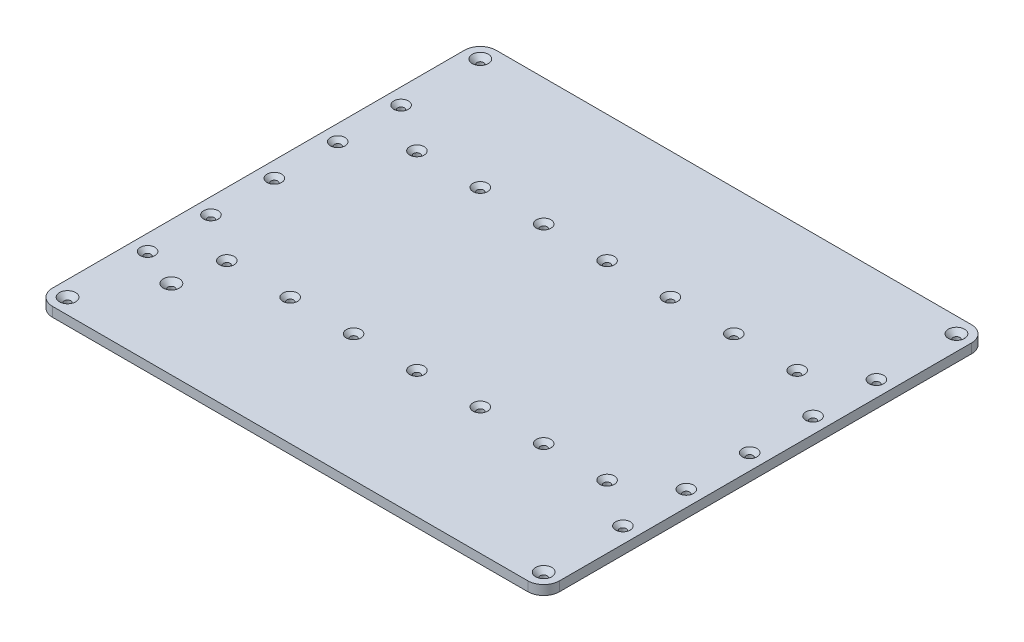
SolidWorks part; units mm, degrees
ref_plane "前视基准面" through (0, 0, 0) normal (0, 0, 1) x (1, 0, 0)
ref_plane "上视基准面" through (0, 0, 0) normal (0, 1, 0) x (1, 0, 0)
ref_plane "右视基准面" through (0, 0, 0) normal (1, 0, 0) x (0, 0, -1)
other "Configuration Table"
sketch "草图1" plane through (0, 0, 0) normal (0, 1, 0) x (1, 0, 0)
  line L1 (-150, -140) -> (150, -140)
  line L2 (-160, -130) -> (-160, 130)
  line L3 (-150, 140) -> (150, 140)
  line L4 (160, -130) -> (160, 130)
  line L5 (-160, -140) -> (-156.8729, -137.2638) construction
  line L6 (-160, 140) -> (-156.8729, 137.2638) construction
  line L8 (156.8729, 137.2638) -> (160, 140) construction
  line L9 (156.8729, -137.2638) -> (160, -140) construction
  arc A0 (150, -140) -> (160, -130) centre (150, -130) ccw
  arc A1 (-160, 130) -> (-150, 140) centre (-150, 130) cw
  arc A2 (-150, -140) -> (-160, -130) centre (-150, -130) cw
  arc A3 (150, 140) -> (160, 130) centre (150, 130) cw
  point P0 (0, 0)
  dimension "D3" = 10
  dimension "D1" = 320
  dimension "D2" = 280
extrude "凸台-拉伸1" add sketch "草图1" along normal mid plane 6
sketch "草图5" plane through (0, 3, 0) normal (0, 1, 0) x (1, 0, 0)
  line L0 (0, 0) -> (0, 142.7283) construction
  line L1 (160, 0) -> (-160, 0) construction
  line L2 (-160, 130) -> (-160, -130) construction
  line L3 (150, 140) -> (-150, 140) construction
  circle A0 centre (0, 60) radius 2.1
  circle A16 centre (40, 60) radius 2.1
  circle A17 centre (80, 60) radius 2.1
  circle A18 centre (120, 60) radius 2.1
  circle A19 centre (-120, 60) radius 2.1
  circle A20 centre (-80, 60) radius 2.1
  circle A21 centre (-40, 60) radius 2.1
  circle A22 centre (-40, -60) radius 2.1
  circle A23 centre (-80, -60) radius 2.1
  circle A24 centre (-120, -60) radius 2.1
  circle A25 centre (120, -60) radius 2.1
  circle A26 centre (80, -60) radius 2.1
  circle A27 centre (40, -60) radius 2.1
  circle A28 centre (0, -60) radius 2.1
  circle A29 centre (-150, 0) radius 2.1
  circle A30 centre (-150, -40) radius 2.1
  circle A31 centre (-150, -80) radius 2.1
  circle A32 centre (-150, 80) radius 2.1
  circle A33 centre (-150, 40) radius 2.1
  circle A34 centre (150, 40) radius 2.1
  circle A35 centre (150, 80) radius 2.1
  circle A36 centre (150, -80) radius 2.1
  circle A37 centre (150, -40) radius 2.1
  circle A38 centre (150, 0) radius 2.1
  dimension "D2" = 4.2
  dimension "D1" = 4.2
  dimension "D3" = 10
  dimension "D4" = 80
extrude "切除-拉伸4" cut sketch "草图5" against normal blind 240
chamfer "倒角2" distance 2.5 angle 45 24 edges at (150, 3, 37.9) (150, 3, 77.9) (120, 3, 57.9) (80, 3, 57.9) (40, 3, 57.9) (0, 3, 57.9) (-40, 3, 62.1) (-80, 3, 62.1) (-120, 3, 62.1) (-150, 3, 82.1) (-150, 3, 42.1) (-150, 3, 2.1) (-150, 3, -42.1) (-150, 3, -82.1) (-120, 3, -62.1) (-80, 3, -62.1) (-40, 3, -62.1) (0, 3, -57.9) (40, 3, -57.9) (150, 3, -2.1) (150, 3, -37.9) (80, 3, -57.9) (120, 3, -57.9) (150, 3, -77.9)
sketch "草图6" plane through (0, 3, 0) normal (0, 1, 0) x (1, 0, 0)
  line L0 (150, 140) -> (-150, 140) construction
  line L1 (-160, 130) -> (-160, -130) construction
  line L2 (160, -130) -> (160, 130) construction
  line L3 (-150, -140) -> (150, -140) construction
  circle A0 centre (-150.25, 130.25) radius 2.1
  circle A1 centre (150.25, 130.25) radius 2.1
  circle A2 centre (150.25, -130.25) radius 2.1
  circle A3 centre (-150.25, -130.25) radius 2.1
  dimension "D1" = 4.2
  dimension "D4" = 4.2
  dimension "D6" = 4.2
  dimension "D8" = 4.2
  dimension "D2" = 9.75
  dimension "D3" = 9.75
  dimension "D5" = 9.75
  dimension "D7" = 9.75
  dimension "D9" = 9.75
extrude "切除-拉伸5" cut sketch "草图6" against normal blind 10
chamfer "倒角3" distance 3 angle 45 4 edges at (150.25, 3, 132.35) (150.25, 3, -128.15) (-150.25, 3, -128.15) (-150.25, 3, 132.35)
sketch "草图7" plane through (0, -3, 0) normal (0, -1, 0) x (-1, 0, 0)
  line L0 (160, 130) -> (160, -130) construction
  line L1 (150, -140) -> (-150, -140) construction
  circle A0 centre (125, -90) radius 2.1
  dimension "D1" = 4.2
  dimension "D2" = 35
  dimension "D3" = 50
extrude "切除-拉伸6" cut sketch "草图7" against normal blind 10
chamfer "倒角4" distance 3 angle 45 1 edges at (-125, 3, 92.1)
